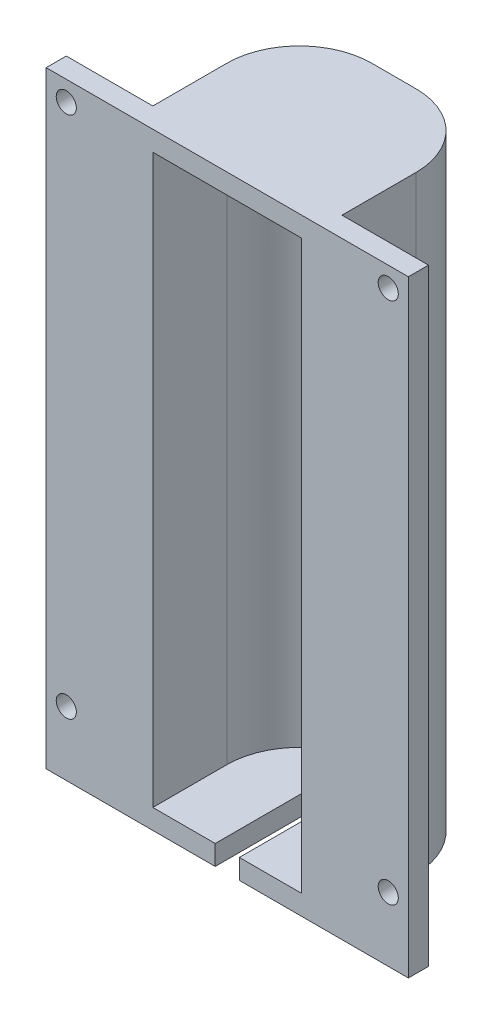
SolidWorks part; units mm, degrees
ref_plane "Front Plane" through (0, 0, 0) normal (0, 0, 1) x (1, 0, 0)
ref_plane "Top Plane" through (0, 0, 0) normal (0, 1, 0) x (1, 0, 0)
ref_plane "Right Plane" through (0, 0, 0) normal (1, 0, 0) x (0, 0, -1)
sketch "Sketch1" plane through (0, 0, 0) normal (0, 0, 1) x (1, 0, 0)
  line L0 (22.5, -37.725) -> (22.5, 37.725)
  line L1 (-9.25, -35.25) -> (9.25, -35.25)
  line L2 (-9.25, -35.25) -> (-9.25, 35.25)
  line L3 (-9.25, 35.25) -> (9.25, 35.25)
  line L4 (9.25, -35.25) -> (9.25, 35.25)
  line L5 (-9.25, -35.25) -> (9.25, 35.25) construction
  line L6 (-9.25, 35.25) -> (9.25, -35.25) construction
  line L7 (-22.5, 37.725) -> (22.5, 37.725)
  line L8 (-22.5, -37.725) -> (-22.5, 37.725)
  line L9 (-22.5, -37.725) -> (22.5, -37.725)
  line L10 (0, -35) -> (0, 0) construction
  line L11 (-1.5, -35.25) -> (-1.5, -37.725)
  line L12 (1.5, -35.25) -> (1.5, -37.725)
  line L13 (-20, -29.75) -> (-20, 35.25) construction
  line L14 (-20, 35.25) -> (20, 35.25) construction
  line L15 (20, -29.75) -> (20, 35.25) construction
  line L16 (-20, -29.75) -> (20, -29.75) construction
  line L17 (0, 35.25) -> (0, 37.725) construction
  line L18 (9.25, 0) -> (22.5, 0) construction
  line L19 (-9.25, 0) -> (-22.5, 0) construction
  point P0 (0, 0)
  point P20 (-66.3475, 3.7955)
  point P27 (0, 0)
  dimension "D1" = 70.5
  dimension "D2" = 65
  dimension "D4" = 40
  dimension "D3" = 18.5
  dimension "D5" = 45
  dimension "D6" = 75.45
  dimension "D7" = 3
  dimension "D8" = 20
extrude "Boss-Extrude1" add sketch "Sketch1" along normal blind 18.2 contours L1 L12 L9 L0 L7 L8 L11 L2 L3 L4 region at (12, -36.8465, 0)
extrude "Boss-Extrude2" add sketch "Sketch1<3>" against normal blind 5.5 contours L1 L12 L9 L0 L7 L8 L11 L2 L3 L4 | L1 L4 L3 L2 | L12 L1 L11 L9 region at (12, -36.8465, 0) region at (0, -36.4875, 0) region at (0, 0, 0)
sketch "Sketch1<3>" plane through (0, 0, 0) normal (0, 0, 1) x (1, 0, 0) same geometry as "Sketch1"
fillet "Fillet1" radius 9 2 edges at (-9.25, 0, 0) (9.25, 0, 0)
sketch "Sketch4" plane through (0, -37.725, 0) normal (0, -1, 0) x (1, 0, 0)
  line L1 (-22.75, 15.7) -> (-11.75, 15.7)
  line L2 (-22.75, 15.7) -> (-22.75, -5.5)
  line L3 (-22.75, -5.5) -> (-11.75, -5.5)
  line L4 (-11.75, 15.7) -> (-11.75, -5.5)
  line L5 (0, 0) -> (0, 18.2) construction
  line L6 (-9.25, 18.2) -> (9.25, 18.2) construction
  line L7 (-9.25, 18.2) -> (-9.25, 9) construction
  line L8 (11.75, -2.5) -> (-11.75, -2.5)
  line L9 (0, -2.5) -> (0, -5.5)
  line L10 (11.75, -5.5) -> (-11.75, -5.5)
  line L11 (-11.75, -2.5) -> (-11.75, -5.5)
  line L12 (-22.5, 18.2) -> (-1.5, 18.2) construction
  line L13 (-22.5, -5.5) -> (22.5, -5.5) construction
  line L14 (11.75, -2.5) -> (11.75, -5.5)
  line L15 (22.75, -5.5) -> (11.75, -5.5)
  line L16 (11.75, 15.7) -> (11.75, -5.5)
  line L17 (22.75, 15.7) -> (11.75, 15.7)
  line L18 (22.75, 15.7) -> (22.75, -5.5)
  point P25 (0, 0)
  line M14 (-22.5, 18.2) -> (-22.5, -5.5)
  line M15 (-22.5, -5.5) -> (22.5, -5.5)
  line M16 (22.5, -5.5) -> (22.5, 18.2)
  dimension "D1" = 2.5
  dimension "D2" = 2.5
  dimension "D3" = 2.5
  dimension "D4" = 11
extrude "Cut-Extrude1" cut sketch "Sketch4" against normal blind 103 contours L14 L8 L9 M15 | L17 L16 L14 M16 M15 | L9 L8 L4 M15 | L4 L1 M14 M15 region at (-17.125, -37.725, 5.1) region at (-5.875, -37.725, -4) region at (5.875, -37.725, -4) region at (17.125, -37.725, 5.1)
sketch "Sketch2" plane through (0, 0, -5.5) normal (0, 0, -1) x (-1, 0, 0)
  point P0 (20, 35.25)
  point P3 (-20, 35.25)
  point P6 (-20, -29.75)
  point P9 (20, -29.75)
  point P12 (-20, 35.25)
  point P14 (20, 35.25)
  point P16 (20, -29.75)
  point P18 (-20, -29.75)
  point P22 (-20, 35.25)
  point P24 (20, 35.25)
  point P26 (-20, 35.25)
  point P28 (20, 35.25)
  point P30 (20, -29.75)
  point P32 (-20, -29.75)
  point P33 (-20, 35.25)
  point P35 (20, 35.25)
  point P37 (20, -29.75)
  point P39 (-20, -29.75)
hole_wizard "Tap Drill for M3 Tap1" positions "Sketch2" profile "Sketch3" hole size "M3" standard "ISO" end condition through all
sketch "Sketch3" plane through (-20, 35.25, -5.5) normal (1, 0, 0) x (0, 1, 0)
  line L0 (0, 0) -> (0, 23.7)
  line L1 (0, 23.7) -> (1.25, 23.7)
  line L2 (1.25, 23.7) -> (1.25, 0.025)
  line L3 (1.25, 0.025) -> (1.275, 0)
  line L5 (1.275, 0) -> (0, 0)
  line L6 (-1.25, 0.025) -> (-1.275, 0) construction
  line L11 (0, -6.35) -> (0, 107.95) construction
  dimension "Thru Hole Dia." = 2.5
  dimension "Thru Hole Depth" = 23.7
  dimension "Near C'Sink Dia." = 2.55
  dimension "Near C'Sink Angle" = 90
fillet "Fillet2" radius 9 2 edges at (-11.75, 0, -2.5) (11.75, 0, -2.5)
